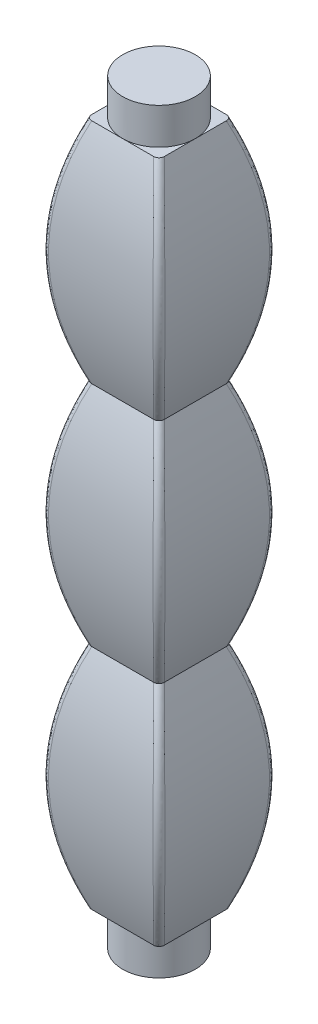
SolidWorks part; units mm, degrees
ref_plane "Front Plane" through (0, 0, 0) normal (0, 0, 1) x (1, 0, 0)
ref_plane "Top Plane" through (0, 0, 0) normal (0, 1, 0) x (1, 0, 0)
ref_plane "Right Plane" through (0, 0, 0) normal (1, 0, 0) x (0, 0, -1)
sketch "Sketch1" plane through (0, 0, 0) normal (0, 0, 1) x (1, 0, 0)
  line L0 (0, 3.2665) -> (2.5, 3.2665)
  line L1 (0, -5.1135) -> (0, 29.2665) construction
  line L5 (2.5, 3.2665) -> (2.5, 5.7665)
  line L14 (-37.8853, 29.2665) -> (41.7137, 29.2665) construction
  line L16 (2.5, 52.7665) -> (2.5, 55.2665) construction
  line L17 (0, 3.2665) -> (0, 29.2665)
  line L18 (0, 63.6465) -> (0, 55.2665) construction
  line L19 (2.5, 5.7665) -> (2.5, 3.2665) construction
  line L20 (2.5, 55.2665) -> (2.5, 52.7665)
  line L21 (0, 55.2665) -> (2.5, 55.2665)
  line L22 (0, 29.2665) -> (0, 5.9372) construction
  line L23 (0, 55.2665) -> (0, 29.2665)
  line L25 (2.5, 52.7665) -> (0.8575, 52.7665)
  line L27 (2.5, 5.7665) -> (0.8575, 5.7665)
  line L28 (0.8575, 52.7665) -> (0.8575, 5.7665)
  point P3 (0, 3.1872)
  point P18 (0, 55.3457)
  point P26 (2.7717, 38.2468)
  dimension "D1" = 2.5
  dimension "D2" = 2.5
  dimension "D3" = 52
  dimension "D4" = 2.5
revolve "Revolve1" add sketch "Sketch1" angle 360 about L17
ref_plane "Plane1" through (0, 52.7665, 0) normal (0, -1, 0) x (-1, 0, 0)
ref_plane "Plane2" through (0, 5.7665, 0) normal (0, 1, 0) x (1, 0, 0)
sketch "Sketch2" plane through (0, 52.7665, 0) normal (0, -1, 0) x (-1, 0, 0)
  line L1 (-2.5, -2.5) -> (2.5, -2.5)
  line L2 (-2.5, -2.5) -> (-2.5, 2.5)
  line L3 (-2.5, 2.5) -> (2.5, 2.5)
  line L4 (2.5, -2.5) -> (2.5, 2.5)
  line L5 (-2.5, -2.5) -> (2.5, 2.5) construction
  line L6 (-2.5, 2.5) -> (2.5, -2.5) construction
  point P0 (0, 0)
  dimension "D2" = 5
sketch "Sketch3" plane through (0, 5.7665, 0) normal (0, 1, 0) x (1, 0, 0)
  line L1 (-2.5, -2.5) -> (2.5, -2.5)
  line L2 (-2.5, -2.5) -> (-2.5, 2.5)
  line L3 (-2.5, 2.5) -> (2.5, 2.5)
  line L4 (2.5, -2.5) -> (2.5, 2.5)
  line L5 (-2.5, -2.5) -> (2.5, 2.5) construction
  line L6 (-2.5, 2.5) -> (2.5, -2.5) construction
  point P0 (0, 0)
  dimension "D1" = 5
ref_plane "Plane3" through (0, 21.4331, 0) normal (0, 1, 0) x (1, 0, 0)
ref_plane "Plane4" through (0, 37.0998, 0) normal (0, -1, 0) x (-1, 0, 0)
sketch "Sketch4" plane through (0, 21.4331, 0) normal (0, 1, 0) x (1, 0, 0)
  line L1 (-2.5, -2.5) -> (2.5, -2.5)
  line L2 (-2.5, -2.5) -> (-2.5, 2.5)
  line L3 (-2.5, 2.5) -> (2.5, 2.5)
  line L4 (2.5, -2.5) -> (2.5, 2.5)
  line L5 (-2.5, -2.5) -> (2.5, 2.5) construction
  line L6 (-2.5, 2.5) -> (2.5, -2.5) construction
sketch "Sketch5" plane through (0, 37.0998, 0) normal (0, -1, 0) x (-1, 0, 0)
  line L1 (-2.5, -2.5) -> (2.5, -2.5)
  line L2 (-2.5, -2.5) -> (-2.5, 2.5)
  line L3 (-2.5, 2.5) -> (2.5, 2.5)
  line L4 (2.5, -2.5) -> (2.5, 2.5)
  line L5 (-2.5, -2.5) -> (2.5, 2.5) construction
  line L6 (-2.5, 2.5) -> (2.5, -2.5) construction
  point P0 (0, 0)
ref_plane "Plane5" through (0, 44.9331, 0) normal (0, -1, 0) x (-1, 0, 0)
sketch "Sketch6" plane through (0, 44.9331, 0) normal (0, -1, 0) x (-1, 0, 0)
  line L1 (-4, -4) -> (4, -4)
  line L2 (-4, -4) -> (-4, 4)
  line L3 (-4, 4) -> (4, 4)
  line L4 (4, -4) -> (4, 4)
  line L5 (-4, -4) -> (4, 4) construction
  line L6 (-4, 4) -> (4, -4) construction
  point P0 (0, 0)
  dimension "D1" = 8
loft "Loft1" add profiles "Sketch2", "Sketch6", "Sketch5" start constraint default end constraint default connector at (2.5, 52.7665, 2.5) connector at (4, 44.9331, 4) connector at (2.5, 37.0998, 2.5)
pattern_linear "LPattern1" count 3 spacing 15.666 along (0, -1, 0) of "Loft1"
fillet "Fillet5" radius 0.4 12 edges
